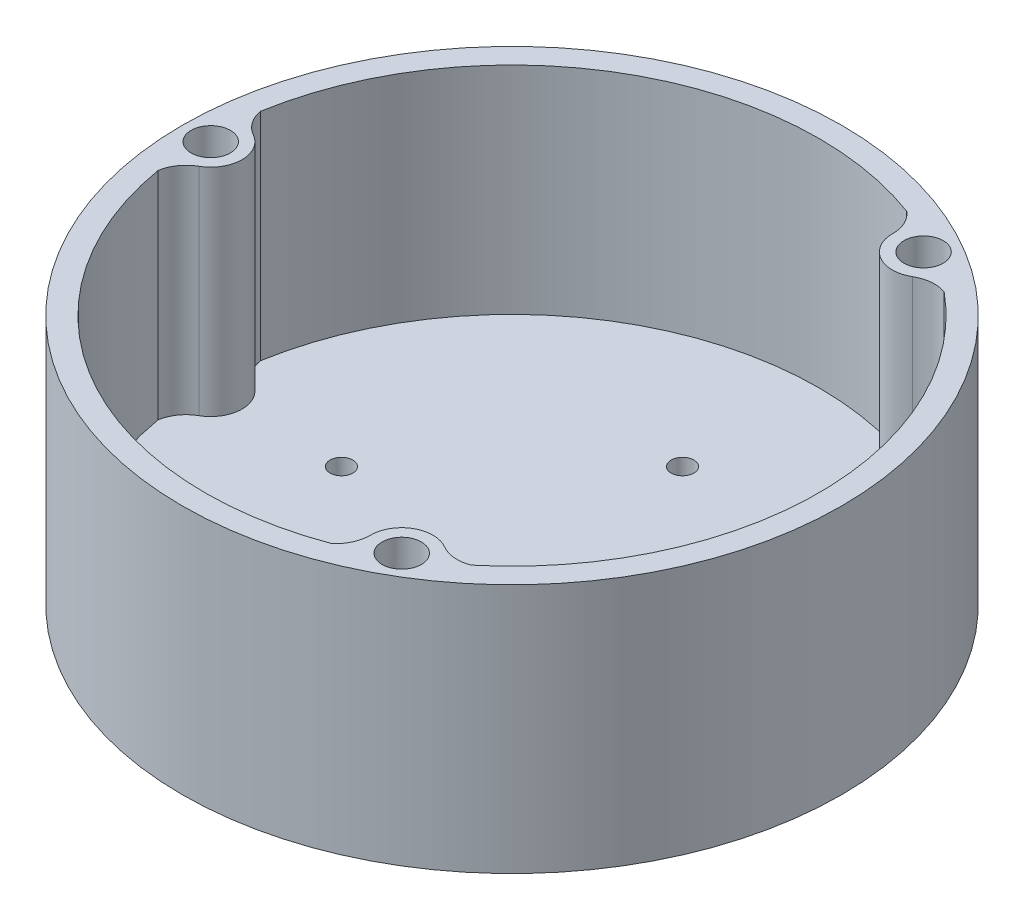
SolidWorks part; units mm, degrees
ref_plane "Front Plane" through (0, 0, 0) normal (0, 0, 1) x (1, 0, 0)
ref_plane "Top Plane" through (0, 0, 0) normal (0, 1, 0) x (1, 0, 0)
ref_plane "Right Plane" through (0, 0, 0) normal (1, 0, 0) x (0, 0, -1)
sketch "Sketch1" plane through (0, 0, 0) normal (0, 1, 0) x (1, 0, 0)
  line L0 (0, 0) -> (0, 15) construction
  line L1 (0, 0) -> (13.25, 22.9497) construction
  circle A0 centre (0, 0) radius 23 construction
  circle A1 centre (0, 0) radius 29
  circle A2 centre (0, 15) radius 1
  circle A3 centre (15, 0) radius 1
  circle A4 centre (0, -15) radius 1
  circle A5 centre (-15, 0) radius 1
  arc A6 (9.4141, 25.3056) -> (-26.6224, 4.5) centre (0, 0) ccw
  circle A7 centre (13.25, 22.9497) radius 1.725
  arc A8 (9.4141, 25.3056) -> (10.5001, 22.9716) centre (7.5002, 22.9954) cw
  arc A9 (10.5001, 22.9716) -> (14.6439, 20.5791) centre (13.25, 22.9497) ccw
  arc A10 (14.6439, 20.5791) -> (17.2083, 20.8056) centre (16.1645, 17.9931) cw
  circle A11 centre (13.25, -22.9497) radius 1.725
  arc A12 (14.6439, -20.5791) -> (10.5001, -22.9716) centre (13.25, -22.9497) ccw
  arc A13 (10.5001, -22.9716) -> (9.4141, -25.3056) centre (7.5002, -22.9954) cw
  arc A14 (17.2083, -20.8056) -> (14.6439, -20.5791) centre (16.1645, -17.9931) cw
  circle A15 centre (-26.5, 0) radius 1.725
  arc A16 (-25.144, -2.3924) -> (-25.144, 2.3924) centre (-26.5, 0) ccw
  arc A17 (-25.144, 2.3924) -> (-26.6224, 4.5) centre (-23.6647, 5.0024) cw
  arc A18 (-26.6224, -4.5) -> (-25.144, -2.3924) centre (-23.6647, -5.0024) cw
  arc A19 (17.2083, -20.8056) -> (17.2083, 20.8056) centre (0, 0) ccw
  arc A21 (-26.6224, -4.5) -> (9.4141, -25.3056) centre (0, 0) ccw
  point P26 (11.875, 20.5681)
  dimension "D1" = 2
  dimension "D5" = 46
  dimension "D6" = 58
  dimension "D8" = 3.45
  dimension "D10" = 2.75
  dimension "D12" = 3
  dimension "D2" = 15
  dimension "D3" = 4
  dimension "D4" = 2
  dimension "D7" = 26.5
  dimension "D9" = 60
  dimension "D11" = 9
  dimension "D14" = 3
extrude "Boss-Extrude1" add sketch "Sketch1" along normal blind 22 contours A1 A21 A18 A16 A17 A6 A8 A9 A10 A19 A14 A12 A13 A15 A11 A7 | A15 | A7 | A11 region at (-28.918, 0, 0)
extrude "Boss-Extrude2" add sketch "Sketch1<5>" along normal blind 3 contours A18 A21 A13 A12 A14 A19 A10 A9 A8 A6 A17 A16 A2 A3 A4 A5 region at (0, 0, 0)
sketch "Sketch1<5>" plane through (0, 0, 0) normal (0, 1, 0) x (1, 0, 0) same geometry as "Sketch1"
extrude "Cut-Extrude1" cut sketch "Sketch1<6>" against normal blind 3 from surface contours A15 | A7 | A11 starting at face at (0, 22, 0)
sketch "Sketch1<6>" plane through (0, 0, 0) normal (0, 1, 0) x (1, 0, 0) same geometry as "Sketch1"
equation "\"motor-dia\" = 46"
equation "\"motor-holes-rad\" = 15"
equation "\"motor-height\" = 21"
equation "\"motor-case-thickness\" = 2"
equation "\"D2@Sketch1\"=\"motor-holes-rad\""
equation "\"D4@Sketch1\"=\"motor-case-thickness\""
equation "\"D5@Sketch1\"=\"motor-dia\""
equation "\"D1@Boss-Extrude2\"= \"motor-height\" + 1"
equation "\"D1@Boss-Extrude1\"=\"motor-height\"+1"
